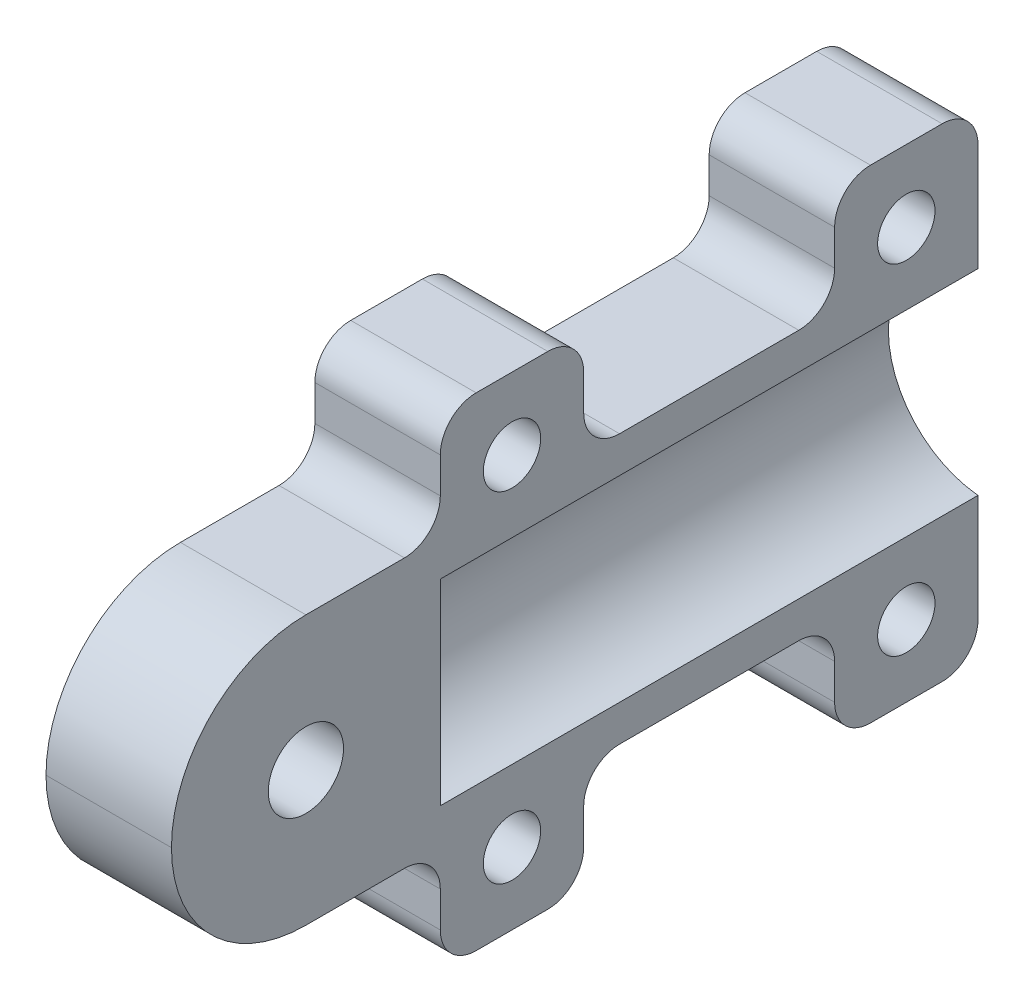
SolidWorks part; units mm, degrees
ref_plane "正面" through (0, 0, 0) normal (0, 0, 1) x (1, 0, 0)
ref_plane "平面" through (0, 0, 0) normal (0, 1, 0) x (1, 0, 0)
ref_plane "右側面" through (0, 0, 0) normal (1, 0, 0) x (0, 0, -1)
sketch "ｽｹｯﾁ1" plane through (0, 0, 0) normal (0, 0, 1) x (1, 0, 0)
  line L1 (-7.5, -7.5) -> (7.5, -7.5)
  line L2 (-7.5, -7.5) -> (-7.5, 7.5)
  line L3 (-7.5, 7.5) -> (7.5, 7.5)
  line L4 (7.5, -7.5) -> (7.5, 7.5)
  line L5 (-7.5, -7.5) -> (7.5, 7.5) construction
  line L6 (-7.5, 7.5) -> (7.5, -7.5) construction
  circle A0 centre (0, 0) radius 5.5
  dimension "D1" = 11
  dimension "D3" = 15
  dimension "D4" = 15
extrude "ﾎﾞｽ - 押し出し1" add sketch "ｽｹｯﾁ1" along normal blind 45
sketch "ｽｹｯﾁ5" plane through (0, 0, 45) normal (0, 0, 1) x (1, 0, 0)
  line L1 (7.5, -7.5) -> (-7.5, -7.5)
  line L2 (7.5, -7.5) -> (7.5, 7.5)
  line L3 (7.5, 7.5) -> (-7.5, 7.5)
  line L4 (-7.5, -7.5) -> (-7.5, 7.5)
  line L5 (7.5, -7.5) -> (-7.5, 7.5) construction
  line L6 (7.5, 7.5) -> (-7.5, -7.5) construction
  point P0 (0, 0)
extrude "ﾎﾞｽ - 押し出し3" add sketch "ｽｹｯﾁ5" against normal blind 15
fillet "ﾌｨﾚｯﾄ2" radius 7.5 2 edges at (0, -7.5, 45) (0, 7.5, 45)
sketch "ｽｹｯﾁ6" plane through (7.5, 0, 0) normal (1, 0, 0) x (0, 0, -1)
  circle A0 centre (-37.5, 0) radius 2.1
  dimension "D1" = 4.2
extrude "ｶｯﾄ - 押し出し1" cut sketch "ｽｹｯﾁ6" against normal through all
sketch "ｽｹｯﾁ7" plane through (7.5, 0, 0) normal (1, 0, 0) x (0, 0, -1)
  line L10 (-37.5, -9.5) -> (2, -9.5)
  line L11 (2, -9.5) -> (2, 9.5)
  line L12 (2, 9.5) -> (-37.5, 9.5)
  line L13 (-37.5, -9.5) -> (2, -9.5)
  line L14 (2, -9.5) -> (2, 9.5)
  line L15 (2, 9.5) -> (-37.5, 9.5)
  arc A6 (-37.5, 9.5) -> (-47, 0) centre (-37.5, 0) ccw
  arc A7 (-47, 0) -> (-37.5, -9.5) centre (-37.5, 0) ccw
  arc A8 (-37.5, 9.5) -> (-47, 0) centre (-37.5, 0) ccw
  arc A9 (-47, 0) -> (-37.5, -9.5) centre (-37.5, 0) ccw
  dimension "D1" = 2
extrude "ｶｯﾄ - 押し出し2" cut sketch "ｽｹｯﾁ7" against normal blind 8
sketch "ｽｹｯﾁ9" plane through (-0.5, 0, 0) normal (1, 0, 0) x (0, 0, -1)
  line L0 (-30, -5.4772) -> (0, -5.4772) construction
  line L1 (0, -5.4772) -> (-8, -5.4772)
  line L2 (0, -5.4772) -> (0, -13.4772)
  line L3 (0, -13.4772) -> (-8, -13.4772)
  line L4 (-8, -5.4772) -> (-8, -13.4772)
  line L5 (-30, 5.4772) -> (-22, 5.4772)
  line L6 (-30, 5.4772) -> (-30, 13.4772)
  line L7 (-30, 13.4772) -> (-22, 13.4772)
  line L8 (-22, 5.4772) -> (-22, 13.4772)
  line L9 (0, 5.4772) -> (-8, 5.4772)
  line L10 (0, 5.4772) -> (0, 13.4772)
  line L11 (0, 13.4772) -> (-8, 13.4772)
  line L12 (-8, 5.4772) -> (-8, 13.4772)
  line L13 (-22, -5.4772) -> (-30, -5.4772)
  line L14 (-22, -5.4772) -> (-22, -13.4772)
  line L15 (-22, -13.4772) -> (-30, -13.4772)
  line L16 (-30, -5.4772) -> (-30, -13.4772)
  circle A0 centre (-4, -9.4772) radius 1.6
  circle A1 centre (-26, 9.4772) radius 1.6
  circle A2 centre (-26, -9.4772) radius 1.6
  circle A3 centre (-4, 9.4772) radius 1.6
  dimension "D7" = 4
  dimension "D8" = 4
  dimension "D9" = 3.2
  dimension "D10" = 4
  dimension "D11" = 4
  dimension "D12" = 3.2
  dimension "D13" = 3.2
  dimension "D14" = 4
  dimension "D16" = 4
  dimension "D18" = 3.2
  dimension "D1" = 8
  dimension "D2" = 8
  dimension "D3" = 8
  dimension "D4" = 8
  dimension "D5" = 8
  dimension "D6" = 8
  dimension "D15" = 4
  dimension "D17" = 4
extrude "ﾎﾞｽ - 押し出し4" add sketch "ｽｹｯﾁ9" against normal blind 7
fillet "ﾌｨﾚｯﾄ3" radius 2 14 edges at (-4, 7.5, 30) (-4, 13.4772, 30) (-4, 13.4772, 22) (-4, 7.5, 22) (-4, 7.5, 8) (-4, 13.4772, 8) (-4, 13.4772, 0) (-4, -13.4772, 0) (-4, -13.4772, 8) (-4, -7.5, 8) (-4, -7.5, 22) (-4, -13.4772, 22) (-4, -7.5, 30) (-4, -13.4772, 30)
sketch "ｽｹｯﾁ11" plane through (-7.5, 0, 0) normal (-1, 0, 0) x (0, 0, 1)
  circle A0 centre (4, 9.4772) radius 3.5
  circle A1 centre (26, 9.4772) radius 3.5
  circle A2 centre (26, -9.4772) radius 3.5
  circle A3 centre (4, -9.4772) radius 3.5
  dimension "D1" = 7
  dimension "D2" = 7
  dimension "D3" = 7
  dimension "D4" = 7
extrude "ｶｯﾄ - 押し出し3" cut sketch "ｽｹｯﾁ11" against normal blind 3.75
